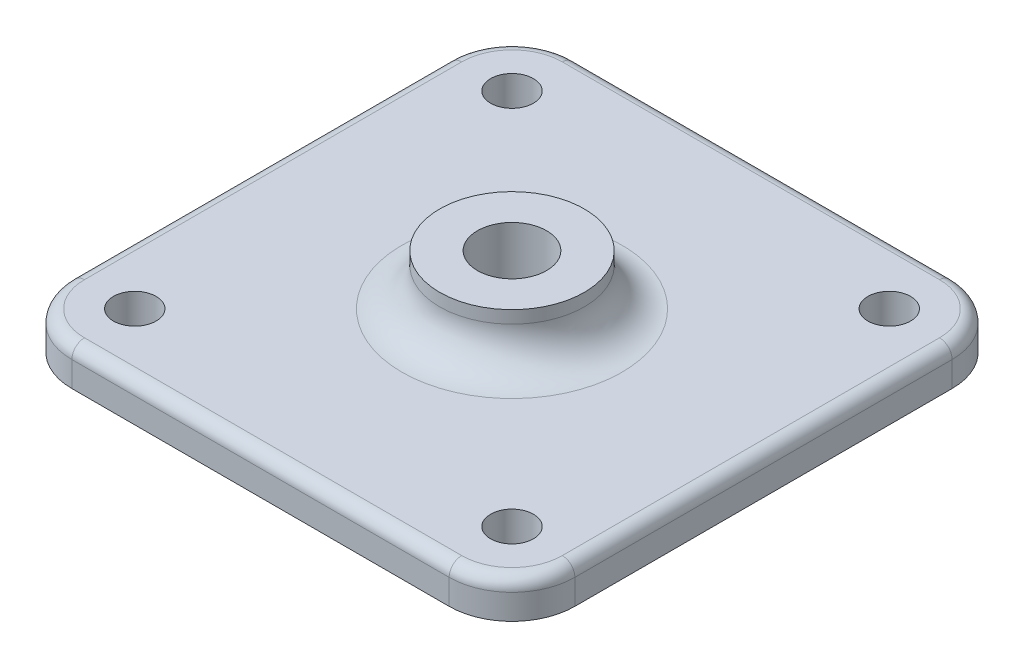
SolidWorks part; units mm, degrees
ref_plane "Front" through (0, 0, 0) normal (0, 0, 1) x (1, 0, 0)
ref_plane "Top" through (0, 0, 0) normal (0, 1, 0) x (1, 0, 0)
ref_plane "Right" through (0, 0, 0) normal (1, 0, 0) x (0, 0, -1)
sketch "Sketch1" plane through (0, 0, 0) normal (0, 1, 0) x (1, 0, 0)
  line L0 (-15, 15) -> (15, 15) construction
  line L1 (-15, -20) -> (15, -20)
  line L2 (-20, -15) -> (-20, 15)
  line L3 (-15, 20) -> (15, 20)
  line L4 (20, -15) -> (20, 15)
  line L5 (-20, -20) -> (20, 20) construction
  line L6 (-20, 20) -> (20, -20) construction
  line L7 (-50, 0) -> (50, 0) construction
  circle A2 centre (-15, 15) radius 1.7
  circle A3 centre (15, 15) radius 1.7
  circle A4 centre (15, -15) radius 1.7
  circle A5 centre (-15, -15) radius 1.7
  arc A6 (15, 20) -> (20, 15) centre (15, 15) cw
  arc A7 (20, -15) -> (15, -20) centre (15, -15) cw
  arc A8 (-15, -20) -> (-20, -15) centre (-15, -15) cw
  arc A9 (-20, 15) -> (-15, 20) centre (-15, 15) cw
  circle A10 centre (0, 0) radius 2.75
  circle A12 centre (0, 0) radius 5.75
  dimension "D5" = 3.4
  dimension "D6" = 3.4
  dimension "D8" = 5
  dimension "D1" = 5.5
  dimension "D3" = 40
  dimension "D4" = 40
  dimension "D7" = 30
  dimension "D2" = 3
extrude "Boss-Extrude1" add sketch "Sketch1" along normal blind 4 contours A12 A10 region at (-5.5874, 0, 0)
extrude "Boss-Extrude2" add sketch "Sketch1<3>" against normal blind 3 contours A12 A10 | A9 L2 A8 L1 A7 L4 A6 L3 A12 A4 A3 A2 A5 region at (-18.1355, 0, 18.1355) region at (-5.5874, 0, 0)
sketch "Sketch1<3>" plane through (0, 0, 0) normal (0, 1, 0) x (1, 0, 0) same geometry as "Sketch1"
fillet "Fillet1" radius 3 1 edges at (0, 0, 5.75)
fillet "Fillet2" radius 1 8 edges at (-18.5355, 0, -18.5355) (-20, 0, 0) (-18.5355, 0, 18.5355) (0, 0, 20) (18.5355, 0, 18.5355) (20, 0, 0) (18.5355, 0, -18.5355) (0, 0, -20)
equation "\"D5@Sketch1\"=\"D6@Sketch1\""
